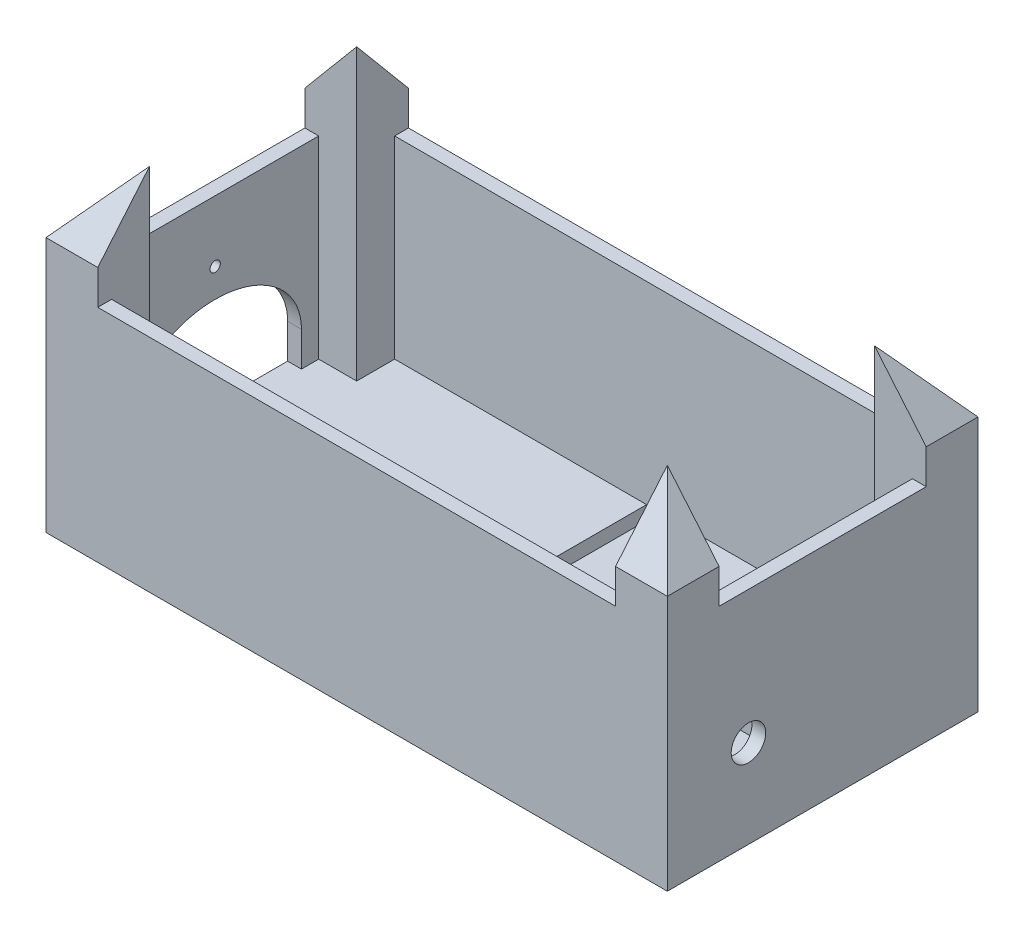
SolidWorks part; units mm, degrees
ref_plane "Front Plane" through (0, 0, 0) normal (0, 0, 1) x (1, 0, 0)
ref_plane "Top Plane" through (0, 0, 0) normal (0, 1, 0) x (1, 0, 0)
ref_plane "Right Plane" through (0, 0, 0) normal (1, 0, 0) x (0, 0, -1)
sketch "Sketch1" plane through (0, 0, 0) normal (0, 1, 0) x (1, 0, 0)
  line L1 (0, 0) -> (180, 0)
  line L2 (0, 0) -> (0, -90)
  line L3 (0, -90) -> (180, -90)
  line L4 (180, 0) -> (180, -90)
  dimension "D1" = 180
  dimension "D2" = 90
extrude "Boss-Extrude1" add sketch "Sketch1" along normal blind 64
shell "Shell1" thickness 4 removed face at (90, 64, 45)
sketch "Sketch2" plane through (180, 0, 0) normal (1, 0, 0) x (0, 0, -1)
  line L1 (-90, 64) -> (-90, 0) construction
  line L2 (-90, 0) -> (0, 0) construction
  circle A0 centre (-66.5, 25.5) radius 5
  dimension "D1" = 10
  dimension "D2" = 25.5
  dimension "D3" = 23.5
extrude "Cut-Extrude1" cut sketch "Sketch2" against normal up to surface (4 mm away) up to face at (176, 34, 45)
sketch "Sketch4" plane through (0, 4, 0) normal (0, 1, 0) x (1, 0, 0)
  line L0 (176, -45) -> (4, -45) construction
  line L1 (176, -86) -> (176, -4) construction
  line L2 (4, -4) -> (4, -86) construction
  line L3 (90, -86) -> (90, -4) construction
  line L4 (4, -86) -> (176, -86) construction
  line L5 (176, -4) -> (4, -4) construction
  circle A0 centre (90, -45) radius 2
  dimension "D1" = 4
extrude "Cut-Extrude2" cut sketch "Sketch4" against normal through all
sketch "Sketch7" plane through (0, 4, 0) normal (0, 1, 0) x (1, 0, 0)
  line L1 (0, 0) -> (15, 0)
  line L2 (0, 0) -> (0, -15)
  line L3 (0, -15) -> (15, -15)
  line L4 (15, 0) -> (15, -15)
  line L5 (180, 0) -> (165, 0)
  line L6 (180, 0) -> (180, -15)
  line L7 (180, -15) -> (165, -15)
  line L8 (165, 0) -> (165, -15)
  line L9 (180, -90) -> (165, -90)
  line L10 (180, -90) -> (180, -75)
  line L11 (180, -75) -> (165, -75)
  line L12 (165, -90) -> (165, -75)
  line L13 (0, -90) -> (15, -90)
  line L14 (0, -90) -> (0, -75)
  line L15 (0, -75) -> (15, -75)
  line L16 (15, -90) -> (15, -75)
  dimension "D1" = 15
  dimension "D2" = 15
  dimension "D3" = 15
  dimension "D4" = 15
  dimension "D5" = 15
  dimension "D6" = 15
  dimension "D7" = 15
  dimension "D8" = 15
extrude "Boss-Extrude3" add sketch "Sketch7" along normal blind 90
sketch "Sketch8" plane through (0, 0, 90) normal (0, 0, 1) x (1, 0, 0)
  line L0 (0, 74) -> (90, 181.2578)
  line L1 (90, 181.2578) -> (180, 74)
  line L2 (180, 74) -> (180, 221.1504)
  line L3 (180, 221.1504) -> (-17.5941, 221.1504)
  line L4 (-17.5941, 221.1504) -> (-17.5941, 74)
  line L5 (-17.5941, 74) -> (0, 74)
  line L6 (0, 94) -> (0, 0) construction
  line L7 (180, 94) -> (180, 0) construction
  line L8 (165, 94) -> (180, 94) construction
  line L9 (0, 94) -> (15, 94) construction
  point P12 (172.5, 94)
  point P13 (-8.797, 74)
  dimension "D1" = 40
  dimension "D2" = 40
  dimension "D3" = 0
  dimension "D4" = 0
  dimension "D5" = 20
  dimension "D6" = 20
  dimension "D7" = 147.1504
  dimension "D8" = 17.5941
extrude "Cut-Extrude4" cut sketch "Sketch8" against normal through all
sketch "Sketch10" plane through (180, 0, 0) normal (1, 0, 0) x (0, 0, -1)
  line L0 (-90, 74) -> (-45, 127.6289)
  line L1 (-45, 127.6289) -> (0, 74)
  line L2 (0, 74) -> (0, 140.5126)
  line L3 (0, 140.5126) -> (-124.3013, 140.5126)
  line L4 (-124.3013, 140.5126) -> (-124.3013, 74)
  line L5 (-124.3013, 74) -> (-90, 74)
  line L6 (-90, 91.8763) -> (-90, 74) construction
  line L7 (0, 91.8763) -> (0, 74) construction
  line L8 (-75, 64) -> (-15, 64) construction
  dimension "D1" = 40
  dimension "D2" = 40
  dimension "D3" = 0
  dimension "D4" = 90
  dimension "D5" = 0
  dimension "D6" = 12.8837
  dimension "D7" = 34.3013
extrude "Cut-Extrude5" cut sketch "Sketch10" against normal through all
hole_wizard "M3x0.5 Tapped Hole1" positions "Sketch12" profile "Sketch13" tap size "M3x0.5" standard "ANSI Metric"
sketch "Sketch12" plane through (0, 0, 0) normal (0, -1, 0) x (-1, 0, 0)
  line L0 (-180, 0) -> (0, 0) construction
  line L1 (-180, -90) -> (-180, 0) construction
  line L2 (0, 0) -> (0, -90) construction
  line L3 (0, -90) -> (-180, -90) construction
  point P0 (-172.5, -7.5)
  point P2 (-7.5, -7.5)
  point P4 (-7.5, -82.5)
  point P6 (-172.5, -82.5)
  dimension "D1" = 7.5
  dimension "D2" = 7.5
  dimension "D3" = 7.5
  dimension "D4" = 7.5
  dimension "D5" = 7.5
  dimension "D6" = 7.5
  dimension "D7" = 7.5
  dimension "D8" = 7.5
sketch "Sketch13" plane through (172.5, 0, 7.5) normal (1, 0, 0) x (0, 0, -1)
  line L0 (0, 0) -> (0, 8.2511)
  line L1 (0, 8.2511) -> (1.25, 7.5)
  line L2 (1.25, 7.5) -> (1.25, 0)
  line L5 (1.25, 0) -> (0, 0)
  line L10 (0, 8.2511) -> (-1.25, 7.5) construction
  line L11 (0, -6.35) -> (0, 107.95) construction
  dimension "Tap Drill Dia." = 2.5
  dimension "Tap Drill Depth" = 7.5
  dimension "Drill Angle" = 118
sketch "Sketch17" plane through (0, 4, 0) normal (0, 1, 0) x (1, 0, 0)
  line L0 (165, -4) -> (15, -4) construction
  line L1 (4, -4) -> (88, -4)
  line L2 (4, -4) -> (4, -43)
  line L3 (4, -43) -> (88, -43)
  line L4 (88, -4) -> (88, -43)
  line L5 (4, -15) -> (4, -75) construction
  line L6 (176, -45) -> (4, -45) construction
  line L7 (176, -75) -> (176, -15) construction
  line L8 (90, -4) -> (90, -86) construction
  line L9 (15, -86) -> (165, -86) construction
  line L10 (176, -4) -> (92, -4)
  line L11 (176, -4) -> (176, -43)
  line L12 (176, -43) -> (92, -43)
  line L13 (92, -4) -> (92, -43)
  line L14 (176, -86) -> (176, -47)
  line L15 (176, -47) -> (92, -47)
  line L16 (176, -86) -> (92, -86)
  line L17 (92, -86) -> (92, -47)
  line L18 (4, -86) -> (4, -47)
  line L19 (4, -86) -> (88, -86)
  line L20 (88, -86) -> (88, -47)
  line L21 (4, -47) -> (88, -47)
  circle A0 centre (90, -45) radius 2 construction
  dimension "D1" = 0
  dimension "D2" = 0
  dimension "D3" = 2
  dimension "D4" = 2
extrude "Boss-Extrude5" add sketch "Sketch17" along normal blind 4
sketch "Sketch15" plane through (0, 0, 0) normal (-1, 0, 0) x (0, 0, 1)
  line L0 (15, 8) -> (43, 8) construction
  line L1 (45, 38) -> (45, 40.2823) construction
  line L3 (0, 74) -> (0, 0) construction
  line L5 (20, 18) -> (20, 8)
  line L6 (20, 8) -> (70, 8)
  line L7 (70, 18) -> (70, 8)
  line L8 (90, 74) -> (90, 0) construction
  ellipse E0 centre (45, 18) end of major axis (70, 18) minor radius 20 (70, 18) -> (20, 18) ccw
  dimension "D1" = 10
  dimension "D2" = 20
  dimension "D3" = 20
  dimension "D4" = 0
  dimension "D5" = 10
  dimension "D6" = 25
  dimension "D7" = 40
extrude "Cut-Extrude6" cut sketch "Sketch15" against normal up to surface (4 mm away) up to face at (4, 21, 45)
sketch "Sketch18" plane through (0, 0, 0) normal (-1, 0, 0) x (0, 0, 1)
  line L0 (10.9, 7.75) -> (79.1, 7.75) construction
  line L1 (45, 8) -> (45, 47.0126) construction
  line L2 (20, 8) -> (70, 8) construction
  line L3 (20, 18) -> (20, 8) construction
  line L4 (70, 8) -> (70, 18) construction
  circle A0 centre (77.75, 7.75) radius 1.5
  circle A2 centre (45, 46.25) radius 1.5
  circle A3 centre (12.25, 7.75) radius 1.5
  point P12 (45, 7.75)
  dimension "D1" = 3
  dimension "D3" = 38.25
  dimension "D6" = 7.75
  dimension "D7" = 0.25
  dimension "D8" = 3
  dimension "D9" = 3
  dimension "D2" = 0.25
  dimension "D4" = 9.1
  dimension "D5" = 7.75
extrude "Cut-Extrude7" cut sketch "Sketch18" against normal blind 10
